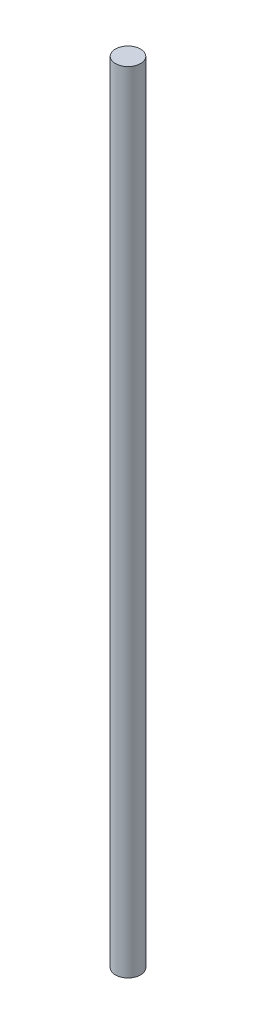
SolidWorks part; units mm, degrees
ref_plane "Front Plane" through (0, 0, 0) normal (0, 0, 1) x (1, 0, 0)
ref_plane "Top Plane" through (0, 0, 0) normal (0, 1, 0) x (1, 0, 0)
ref_plane "Right Plane" through (0, 0, 0) normal (1, 0, 0) x (0, 0, -1)
sketch "Sketch1" plane through (0, 0, 0) normal (0, 1, 0) x (1, 0, 0)
  circle A0 centre (0, 0) radius 4.7625
  dimension "D1" = 9.525
extrude "Boss-Extrude1" add sketch "Sketch1" along normal blind 298.45
equation "\"Mid_Coupler_Length\" = 10in"
equation "\"Lead_Screw_Length\" = (\"Mid_Coupler_Length\" + 2*0.375in + 2*0.5in)"
equation "\"D1@Boss-Extrude1\"=\"Lead_Screw_Length\""
